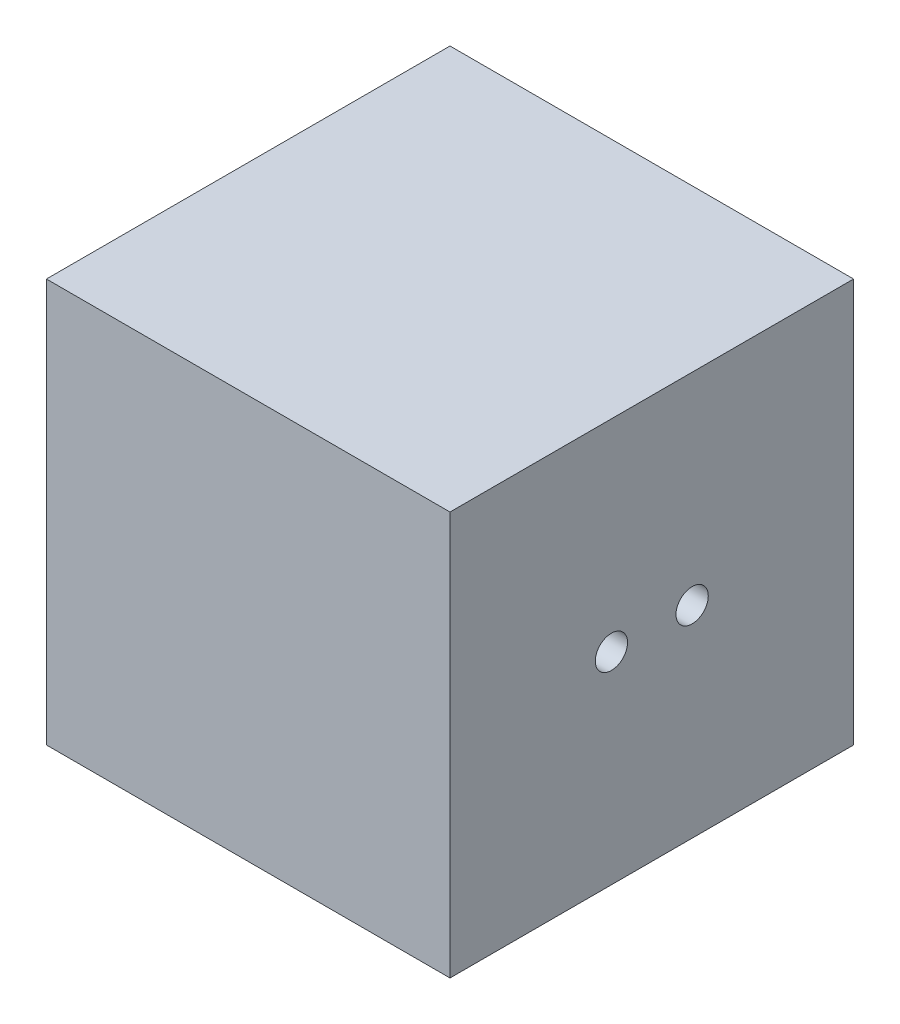
SolidWorks part; units mm, degrees
ref_plane "Plano frontal" through (0, 0, 0) normal (0, 0, 1) x (1, 0, 0)
ref_plane "Plano superior" through (0, 0, 0) normal (0, 1, 0) x (1, 0, 0)
ref_plane "Plano direito" through (0, 0, 0) normal (1, 0, 0) x (0, 0, -1)
sketch "Esboço1" plane through (0, 0, 0) normal (0, 0, 1) x (1, 0, 0)
  line L1 (-50, -50) -> (50, -50)
  line L2 (-50, -50) -> (-50, 50)
  line L3 (-50, 50) -> (50, 50)
  line L4 (50, -50) -> (50, 50)
  line L5 (0, 50) -> (0, -50) construction
  line L6 (-50, 0) -> (50, 0) construction
  point P0 (0, 0)
extrude "Ressalto-extrusão1" add sketch "Esboço1" along normal blind 100
sketch "Esboço2" plane through (50, 0, 0) normal (1, 0, 0) x (0, 0, -1)
  circle A0 centre (-40, 0) radius 4
  circle A1 centre (-60, 0) radius 4
extrude "Corte-extrusão1" cut sketch "Esboço2" against normal up to next
